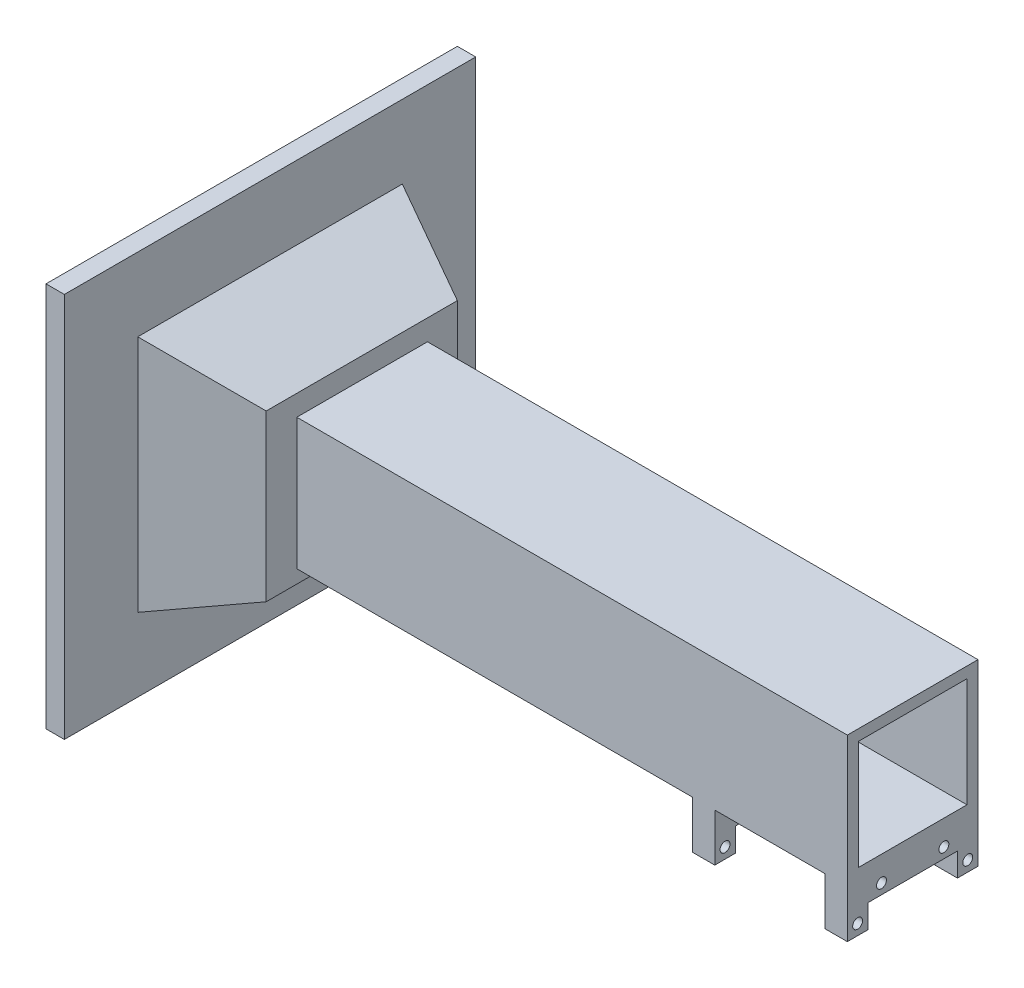
SolidWorks part; units mm, degrees
ref_plane "Front Plane" through (0, 0, 0) normal (0, 0, 1) x (1, 0, 0)
ref_plane "Top Plane" through (0, 0, 0) normal (0, 1, 0) x (1, 0, 0)
ref_plane "Right Plane" through (0, 0, 0) normal (1, 0, 0) x (0, 0, -1)
sketch "Sketch1" plane through (0, 0, 0) normal (0, 1, 0) x (1, 0, 0)
  line L1 (-21.125, -17.8) -> (21.125, -17.8)
  line L2 (-21.125, -17.8) -> (-21.125, 17.8)
  line L3 (-21.125, 17.8) -> (21.125, 17.8)
  line L4 (21.125, -17.8) -> (21.125, 17.8)
  line L5 (-21.125, -17.8) -> (21.125, 17.8) construction
  line L6 (-21.125, 17.8) -> (21.125, -17.8) construction
  point P0 (0, 0)
  dimension "D1" = 42.25
  dimension "D2" = 35.6
extrude "Boss-Extrude1" add sketch "Sketch1" along normal blind 2
sketch "Sketch2" plane through (0, 2, 0) normal (0, 1, 0) x (1, 0, 0)
  line L0 (-21.125, -17.8) -> (21.125, -17.8) construction
  line L1 (-21.125, 17.8) -> (-19.125, 17.8)
  line L2 (-21.125, 17.8) -> (-21.125, -17.8)
  line L3 (-21.125, -17.8) -> (-19.125, -17.8)
  line L4 (-19.125, 17.8) -> (-19.125, -17.8)
  line L6 (21.125, 17.8) -> (19.125, 17.8)
  line L7 (21.125, 17.8) -> (21.125, -17.8)
  line L8 (21.125, -17.8) -> (19.125, -17.8)
  line L9 (19.125, 17.8) -> (19.125, -17.8)
  dimension "D1" = 2
  dimension "D2" = 2
extrude "Boss-Extrude2" add sketch "Sketch2" along normal blind 50
extrude "Cut-Extrude6" cut sketch "Sketch1<2>" along normal blind 20
sketch "Sketch1<2>" plane through (0, 0, 0) normal (0, 1, 0) x (1, 0, 0) same geometry as "Sketch1"
sketch "Sketch8" plane through (0, 20, 0) normal (0, -1, 0) x (1, 0, 0)
  line L1 (-21.125, 17.8) -> (21.125, 17.8)
  line L2 (-21.125, 17.8) -> (-21.125, -17.8)
  line L3 (-21.125, -17.8) -> (21.125, -17.8)
  line L4 (21.125, 17.8) -> (21.125, -17.8)
extrude "Boss-Extrude3" add sketch "Sketch8" along normal blind 2
sketch "Sketch9" plane through (21.125, 0, 0) normal (1, 0, 0) x (0, 0, -1)
  line L1 (-17.8, 18) -> (17.8, 18)
  line L2 (-17.8, 18) -> (-17.8, 5)
  line L3 (-17.8, 5) -> (17.8, 5)
  line L4 (17.8, 18) -> (17.8, 5)
  dimension "D1" = 13
  dimension "D2" = 35.6
extrude "Boss-Extrude4" add sketch "Sketch9" against normal up to surface (42.25 mm away) up to face at (-21.125, 35, 0)
sketch "Sketch12" plane through (0, 0, -17.8) normal (0, 0, -1) x (-1, 0, 0)
  line L0 (21.125, 5) -> (-21.125, 5) construction
  line L1 (-15, 5) -> (15, 5)
  line L2 (-15, 5) -> (-15, 18)
  line L3 (-15, 18) -> (15, 18)
  line L4 (15, 5) -> (15, 18)
  line L5 (19.125, 20) -> (-19.125, 20) construction
  line L6 (21.125, 52) -> (21.125, 5) construction
  dimension "D1" = 2
  dimension "D2" = 30
  dimension "D3" = 6.125
extrude "Cut-Extrude9" cut sketch "Sketch12" against normal through all
sketch "Sketch13" plane through (15, 0, 0) normal (-1, 0, 0) x (0, 0, 1)
  line L0 (-17.8, 5) -> (17.8, 5) construction
  line L1 (-12.2, 5) -> (12.2, 5)
  line L2 (-12.2, 5) -> (-12.2, 18)
  line L3 (-12.2, 18) -> (12.2, 18)
  line L4 (12.2, 5) -> (12.2, 18)
  line L5 (17.8, 52) -> (17.8, 5) construction
  line L6 (-17.8, 52) -> (-17.8, 5) construction
  dimension "D1" = 13
  dimension "D2" = 5.6
  dimension "D3" = 5.6
extrude "Cut-Extrude10" cut sketch "Sketch13" along normal through all and the other way through all
sketch "Sketch15" plane through (-21.125, 0, 0) normal (-1, 0, 0) x (0, 0, 1)
  line L0 (12.2, 18) -> (-12.2, 18) construction
  line L1 (-17.8, 52) -> (-17.8, 5) construction
  line L2 (0, -23.2375) -> (0, 23.2375) construction
  circle A0 centre (-15, 7.9) radius 1.35
  circle A1 centre (15, 7.9) radius 1.35
  dimension "D1" = 2.7
  dimension "D2" = 10.1
  dimension "D3" = 2.8
extrude "Cut-Extrude11" cut sketch "Sketch15" against normal through all
sketch "Sketch16" plane through (21.125, 0, 0) normal (1, 0, 0) x (0, 0, -1)
  line L0 (-17.8, 5) -> (-17.8, 52) construction
  line L1 (-17.8, 18) -> (17.8, 18)
  line L2 (-17.8, 18) -> (-17.8, 53.7547)
  line L3 (-17.8, 53.7547) -> (17.8, 53.7547)
  line L4 (17.8, 18) -> (17.8, 53.7547)
  line L5 (17.8, 5) -> (17.8, 52) construction
  line L6 (-12.2, 18) -> (12.2, 18) construction
  dimension "D1" = 0
extrude "Boss-Extrude5" add sketch "Sketch16" against normal blind 150
sketch "Sketch17" plane through (-128.875, 0, 0) normal (-1, 0, 0) x (0, 0, 1)
  line L1 (26.1448, 14.3823) -> (-25.9429, 14.3823)
  line L2 (26.1448, 14.3823) -> (26.1448, 59.4038)
  line L3 (26.1448, 59.4038) -> (-25.9429, 59.4038)
  line L4 (-25.9429, 14.3823) -> (-25.9429, 59.4038)
ref_plane "Plane1" through (-158.875, 0, 0) normal (-1, 0, 0) x (0, 0, 1)
sketch "Sketch18" plane through (-158.875, 0, 0) normal (-1, 0, 0) x (0, 0, 1)
  line L0 (26.1448, 14.3823) -> (-25.9429, 14.3823) construction
  line L1 (-55.9429, 89.4038) -> (56.1448, 89.4038)
  line L2 (-55.9429, 89.4038) -> (-55.9429, -15.6177)
  line L3 (-55.9429, -15.6177) -> (56.1448, -15.6177)
  line L4 (56.1448, 89.4038) -> (56.1448, -15.6177)
  line L5 (26.1448, 59.4038) -> (-25.9429, 59.4038) construction
  line L6 (26.1448, 14.3823) -> (26.1448, 59.4038) construction
  line L7 (-25.9429, 14.3823) -> (-25.9429, 59.4038) construction
  dimension "D1" = 30
  dimension "D2" = 30
  dimension "D3" = 30
  dimension "D4" = 30
extrude "Boss-Extrude6" add sketch "Sketch18" against normal blind 5 separate body contours L1 L4 L3 L2
sketch "Sketch20" plane through (-153.875, 0, 0) normal (1, 0, 0) x (0, 0, -1)
  line L0 (55.9429, -15.6177) -> (-56.1448, -15.6177) construction
  line L1 (-36.1448, 4.3823) -> (35.9429, 4.3823)
  line L2 (-36.1448, 4.3823) -> (-36.1448, 69.4038)
  line L3 (-36.1448, 69.4038) -> (35.9429, 69.4038)
  line L4 (35.9429, 4.3823) -> (35.9429, 69.4038)
  line L5 (55.9429, 89.4038) -> (-56.1448, 89.4038) construction
  line L6 (55.9429, 89.4038) -> (55.9429, -15.6177) construction
  line L7 (-56.1448, 89.4038) -> (-56.1448, -15.6177) construction
  dimension "D1" = 20
  dimension "D2" = 20
  dimension "D3" = 20
  dimension "D4" = 20
loft "Loft1" add profiles "Sketch20", "Sketch17" connector at (-153.875, 4.3823, 36.1448) connector at (-128.875, 14.3823, 26.1448)
sketch "Sketch21" plane through (21.125, 0, 0) normal (1, 0, 0) x (0, 0, -1)
  line L0 (17.8, 53.7547) -> (-17.8, 53.7547) construction
  line L1 (-14.8, 50.7547) -> (14.8, 50.7547)
  line L2 (-14.8, 50.7547) -> (-14.8, 21)
  line L3 (-14.8, 21) -> (14.8, 21)
  line L4 (14.8, 50.7547) -> (14.8, 21)
  line L5 (17.8, 18) -> (17.8, 53.7547) construction
  line L6 (-17.8, 18) -> (17.8, 18) construction
  line L7 (-17.8, 53.7547) -> (-17.8, 18) construction
  dimension "D1" = 3
  dimension "D2" = 3
  dimension "D3" = 3
  dimension "D4" = 3
extrude "Cut-Extrude13" cut sketch "Sketch21" against normal up to surface (150 mm away) up to face at (-128.875, 35.8773, 0)
sketch "Sketch25" plane through (21.125, 0, 0) normal (1, 0, 0) x (0, 0, -1)
  line L0 (12.2, 18) -> (12.2, 5) construction
  line L1 (-12.2, 18) -> (12.2, 18)
  line L2 (-12.2, 18) -> (-12.2, 11.4)
  line L3 (-12.2, 11.4) -> (12.2, 11.4)
  line L4 (12.2, 18) -> (12.2, 11.4)
  dimension "D1" = 24.4
  dimension "D2" = 6.6
extrude "Boss-Extrude9" add sketch "Sketch25" against normal up to surface (6.125 mm away) up to face at (15, 7.9, -16.35)
sketch "Sketch26" plane through (-15, 0, 0) normal (1, 0, 0) x (0, 0, -1)
  line L0 (-12.2, 18) -> (-12.2, 5) construction
  line L1 (12.2, 18) -> (-12.2, 18)
  line L2 (12.2, 18) -> (12.2, 11.4)
  line L3 (12.2, 11.4) -> (-12.2, 11.4)
  line L4 (-12.2, 18) -> (-12.2, 11.4)
  dimension "D1" = 6.6
extrude "Boss-Extrude10" add sketch "Sketch26" against normal up to surface (6.125 mm away) up to face at (-21.125, 7.9, -13.65)
sketch "Sketch27" plane through (21.125, 0, 0) normal (1, 0, 0) x (0, 0, -1)
  line L0 (-12.2, 11.4) -> (12.2, 11.4) construction
  line L1 (17.8, 5) -> (17.8, 53.7547) construction
  circle A0 centre (8.5, 14.2) radius 1.35
  circle A1 centre (-8.5, 14.2) radius 1.35
  dimension "D1" = 2.7
  dimension "D2" = 2.7
  dimension "D3" = 17
  dimension "D4" = 2.8
  dimension "D5" = 9.3
extrude "Cut-Extrude15" cut sketch "Sketch27" against normal up to surface (42.25 mm away) up to face at (-21.125, 7.9, -13.65)
